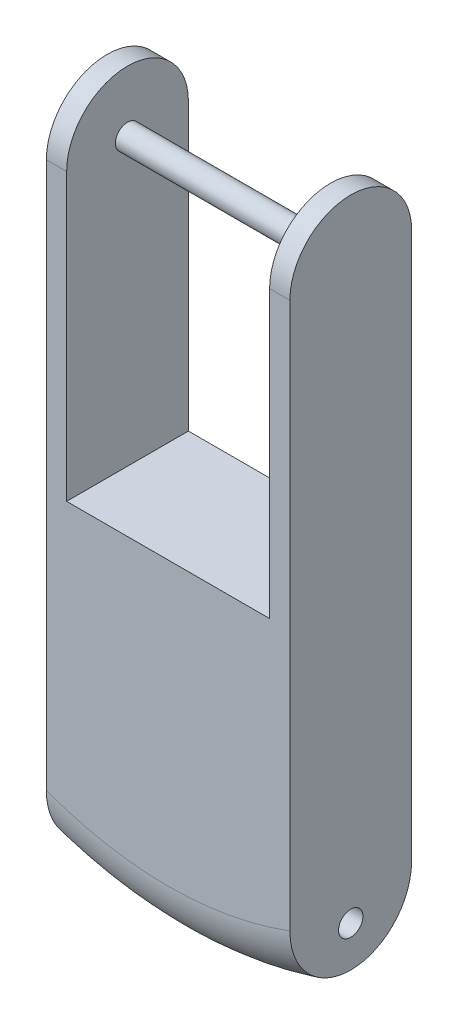
SolidWorks part; units mm, degrees
ref_plane "前视基准面" through (0, 0, 0) normal (0, 0, 1) x (1, 0, 0)
ref_plane "上视基准面" through (0, 0, 0) normal (0, 1, 0) x (1, 0, 0)
ref_plane "右视基准面" through (0, 0, 0) normal (1, 0, 0) x (0, 0, -1)
sketch "草图1" plane through (0, 0, 0) normal (0, 0, 1) x (1, 0, 0)
  line L0 (0, 70) -> (0, -90) construction
  line L2 (30, -95.3939) -> (30, 70)
  line L4 (-30, 70) -> (-30, -95.3939)
  line L6 (0, -90) -> (-50.068, -90) construction
  line L7 (-50.068, -90) -> (-50.068, 70) construction
  line L8 (-50.068, 70) -> (79.7476, 70) construction
  line L9 (-30, 70) -> (30, 70)
  arc A1 (-30, -95.3939) -> (30, -95.3939) centre (0, 0) ccw
  dimension "D1" = 160
extrude "凸台-拉伸1" add sketch "草图1" along normal blind 30
sketch "草图2" plane through (30, 0, 0) normal (1, 0, 0) x (0, 0, -1)
  line L0 (-30, -95.3939) -> (-30, -85.3939) construction
  line L2 (-30, -95.3939) -> (-30, 70) construction
  line L3 (-30, -85.3939) -> (-15, -85.3939) construction
  circle A0 centre (-15, -85.3939) radius 3
  dimension "D3" = 6
  dimension "D1" = 10
  dimension "D2" = 15
extrude "切除-拉伸1" cut sketch "草图2" against normal blind 87
sketch "草图3" plane through (0, 0, 30) normal (0, 0, 1) x (1, 0, 0)
  line L0 (0, 70) -> (0, -100.7832) construction
  line L1 (30, 70) -> (-30, 70) construction
  line L3 (-25, 70) -> (-25, -15.3916)
  line L4 (-25, -15.3916) -> (25, -15.3916)
  line L5 (25, -15.3916) -> (25, 70)
  line L6 (25, 70) -> (-25, 70)
  dimension "D1" = 25
  dimension "D2" = 50
extrude "切除-拉伸2" cut sketch "草图3" against normal blind 87
sketch "草图4" plane through (30, 0, 0) normal (1, 0, 0) x (0, 0, -1)
  line L0 (-30, 70) -> (-15, 70) construction
  line L1 (-30, 70) -> (0, 70) construction
  line L2 (-15, 70) -> (-15, 55) construction
  circle A0 centre (-15, 55) radius 3
  dimension "D3" = 6
  dimension "D1" = 15
  dimension "D2" = 15
extrude "凸台-拉伸2" add sketch "草图4" against normal blind 56
fillet "圆角1" radius 15 1 edges at (0, -100, 30) type face fillet first side face at (0, 6.7279, 30) second side face at (0, -97.697, 15)
fillet "圆角2" radius 15 1 edges at (0, -100, 0) type face fillet first side face at (0, 6.7279, 0) second side face at (0, -97.697, 7.5)
sketch "草图5" plane through (-30, 0, 0) normal (-1, 0, 0) x (0, 0, 1)
  line L3 (30, 55) -> (48.3912, 55)
  line L4 (48.3912, 55) -> (48.3912, 76.5578)
  line L5 (48.3912, 76.5578) -> (-10.7143, 76.5578)
  line L6 (-10.7143, 76.5578) -> (-10.7143, 55)
  line L7 (-10.7143, 55) -> (0, 55)
  arc A0 (30, 55) -> (0, 55) centre (15, 55) ccw
extrude "切除-拉伸3" cut sketch "草图5" against normal blind 85
